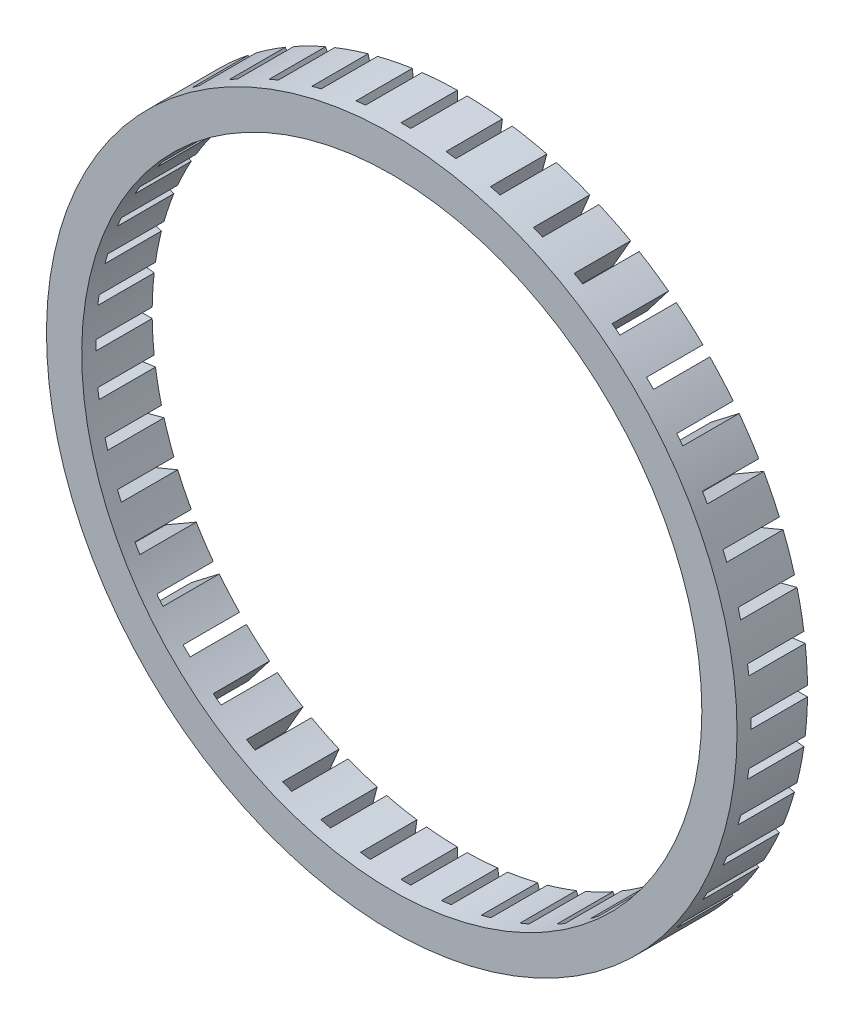
SolidWorks part; units mm, degrees
ref_plane "Front Plane" through (0, 0, 0) normal (0, 0, 1) x (1, 0, 0)
ref_plane "Top Plane" through (0, 0, 0) normal (0, 1, 0) x (1, 0, 0)
ref_plane "Right Plane" through (0, 0, 0) normal (1, 0, 0) x (0, 0, -1)
sketch "Sketch1" plane through (0, 0, 0) normal (0, 0, 1) x (1, 0, 0)
  circle A0 centre (0, 0) radius 44
  circle A1 centre (0, 0) radius 49
  dimension "D1" = 88
  dimension "D2" = 98
extrude "Boss-Extrude1" add sketch "Sketch1" along normal blind 10 contours A1 | A0
sketch "Sketch2" plane through (0, 0, 10) normal (0, 0, 1) x (1, 0, 0)
  line L0 (0, 0) -> (0, 49)
  circle A1 centre (0, 0) radius 49 construction
sketch "Sketch3" plane through (0, 0, 0) normal (0, 1, 0) x (1, 0, 0)
  line L0 (-0.7, 0) -> (-0.7, -8)
  line L1 (-0.7, -8) -> (0.7, -8)
  line L2 (0.7, -8) -> (0.7, 0)
  line L3 (0.7, 0) -> (-0.7, 0)
  point P2 (0, 0)
  dimension "D1" = 8
  dimension "D2" = 1.4
extrude "Cut-Extrude1" cut sketch "Sketch3" against normal through all both and the other way through all
ref_axis "Axis2" through (0, 0, -0.5) along (0, 0, 1)
pattern_circular "CirPattern1" count 48 over 360 about axis through (0, 0, -0.5) along (0, 0, 1) of "Cut-Extrude1"
